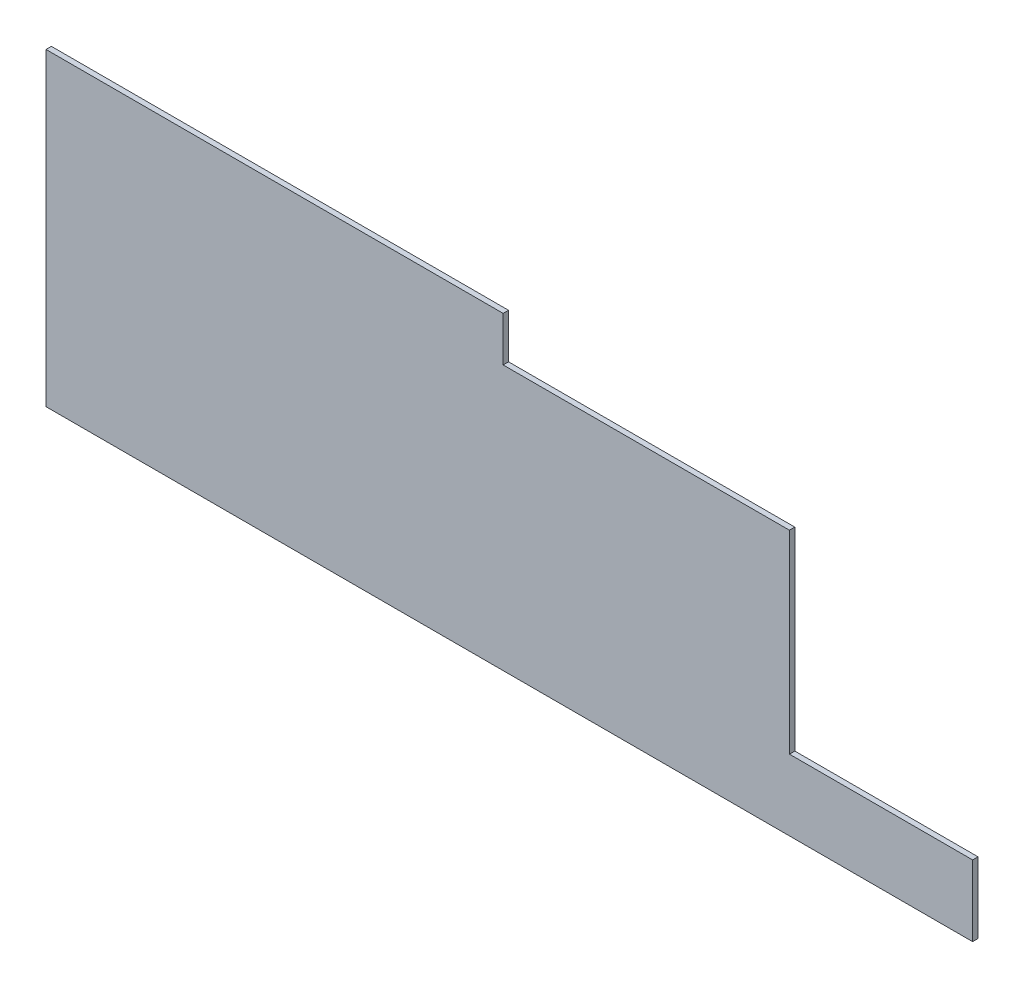
SolidWorks part; units mm, degrees
ref_plane "Ön Düzlem" through (0, 0, 0) normal (0, 0, 1) x (1, 0, 0)
ref_plane "Üst Düzlem" through (0, 0, 0) normal (0, 1, 0) x (1, 0, 0)
ref_plane "Sağ Düzlem" through (0, 0, 0) normal (1, 0, 0) x (0, 0, -1)
sketch "Çizim1" plane through (0, 0, 0) normal (0, 0, 1) x (1, 0, 0)
  line L0 (0, 0) -> (0, 1720)
  line L4 (-6020, 2010) -> (-6020, 0)
  line L5 (-6020, 0) -> (0, 0)
  line L6 (-6020, 2010) -> (-3045, 2010)
  line L7 (-3045, 2010) -> (-3045, 1720)
  line L8 (-3045, 1720) -> (0, 1720)
  dimension "D1" = 1720
  dimension "D2" = 3045
  dimension "D3" = 290
  dimension "D4" = 2010
  dimension "D5" = 2975
  dimension "D6" = 6020
base flange "Taban-Flanş1" sketch "Çizim1" thickness 35 reverse thickness direction no parameters "D1"=3
sketch "Çizim2" plane through (0, 0, 0) normal (0, 0, 1) x (1, 0, 0)
  line L0 (-6020, 0) -> (0, 0) construction
  line L1 (0, 1720) -> (-360, 1720)
  line L2 (0, 1720) -> (0, 460)
  line L3 (0, 460) -> (-360, 460)
  line L4 (-360, 1720) -> (-360, 460)
  line L5 (-3045, 1720) -> (-3045, 2010) construction
  dimension "D1" = 360
  dimension "D2" = 1260
  dimension "D3" = 460
  dimension "D4" = 2685
extrude "Kes-Ekstrüzyon1" cut sketch "Çizim2" against normal through all both and the other way through all
sketch "Çizim3" plane through (0, 0, 0) normal (0, 0, 1) x (1, 0, 0)
  line L0 (-360, 1720) -> (-3045, 1720) construction
  line L1 (-930, 1720) -> (-360, 1720)
  line L2 (-930, 1720) -> (-930, 460)
  line L3 (-930, 460) -> (-360, 460)
  line L4 (-360, 1720) -> (-360, 460)
  line L5 (0, 0) -> (0, 460) construction
  line L6 (-3045, 1720) -> (-3045, 2010) construction
  line L8 (-3045, 2010) -> (-3050, 2010)
  line L9 (-3045, 2010) -> (-3045, 1720)
  line L10 (-3045, 1720) -> (-3050, 1720)
  line L11 (-3050, 2010) -> (-3050, 1720)
  dimension "D1" = 930
  dimension "D2" = 1260
  dimension "D3" = 2115
  dimension "D4" = 2120
extrude "Kes-Ekstrüzyon2" cut sketch "Çizim3" against normal through all both and the other way through all
sketch "Çizim4" plane through (0, 0, 0) normal (0, 0, 1) x (1, 0, 0)
  line L0 (-3050, 2010) -> (-3050, 1720) construction
  line L1 (-930, 1720) -> (-1190, 1720)
  line L2 (-930, 1720) -> (-930, 460)
  line L3 (-930, 460) -> (-1190, 460)
  line L4 (-1190, 1720) -> (-1190, 460)
  line L5 (0, 0) -> (0, 460) construction
  dimension "D1" = 1860
  dimension "D2" = 260
  dimension "D3" = 1260
  dimension "D4" = 1190
extrude "Kes-Ekstrüzyon3" cut sketch "Çizim4" against normal through all both and the other way through all
sketch "Büküm-Çizgileri1" [suppressed] plane through (0, 0, 0) normal (0, 1, 0) x (1, 0, 0)
sketch "Sınırlandırma-Kutusu1" [suppressed] plane through (0, 0, 0) normal (0, 1, 0) x (1, 0, 0)
sheet metal parameters "Sac-Levha1" thickness 35 parameters "D1"=3
flat pattern "Düz-Çoğaltma1" [suppressed]
sketch "Büküm-Çizgileri2" plane through (0, 0, 0) normal (0, 1, 0) x (1, 0, 0)
sketch3d "Sınırlandırma-Kutusu2" [suppressed]
  line L0 (-6020, 0, 0) -> (0, 0, 0) construction
  line L1 (-6020, 2010, 0) -> (0, 2010, 0) construction
  line L2 (-6020, 0, 0) -> (-6020, 2010, 0) construction
  line L3 (0, 0, 0) -> (0, 2010, 0) construction
sheet metal parameters "Sac-Levha2" thickness 35 parameters "D1"=3
flat pattern "Düz-Çoğaltma1"
sketch "Büküm-Çizgileri2" plane through (0, 0, 0) normal (0, 1, 0) x (1, 0, 0)
sketch3d "Sınırlandırma-Kutusu2" [suppressed]
  line L0 (-6020, 0, 0) -> (0, 0, 0) construction
  line L1 (-6020, 2010, 0) -> (0, 2010, 0) construction
  line L2 (-6020, 0, 0) -> (-6020, 2010, 0) construction
  line L3 (0, 0, 0) -> (0, 2010, 0) construction
sheet metal parameters "Sac-Levha3" thickness 35 parameters "D1"=3
flat pattern "Düz-Çoğaltma1"
sketch "Büküm-Çizgileri2" plane through (0, 0, 0) normal (0, 1, 0) x (1, 0, 0)
sketch3d "Sınırlandırma-Kutusu2" [suppressed]
  line L0 (-6020, 0, 0) -> (0, 0, 0) construction
  line L1 (-6020, 2010, 0) -> (0, 2010, 0) construction
  line L2 (-6020, 0, 0) -> (-6020, 2010, 0) construction
  line L3 (0, 0, 0) -> (0, 2010, 0) construction
sheet metal parameters "Sac-Levha4" thickness 35 parameters "D1"=3
flat pattern "Düz-Çoğaltma1"
sketch "Büküm-Çizgileri2" plane through (0, 0, 0) normal (0, 1, 0) x (1, 0, 0)
sketch3d "Sınırlandırma-Kutusu2" [suppressed]
  line L0 (-6020, 0, 0) -> (0, 0, 0) construction
  line L1 (-6020, 2010, 0) -> (0, 2010, 0) construction
  line L2 (-6020, 0, 0) -> (-6020, 2010, 0) construction
  line L3 (0, 0, 0) -> (0, 2010, 0) construction
